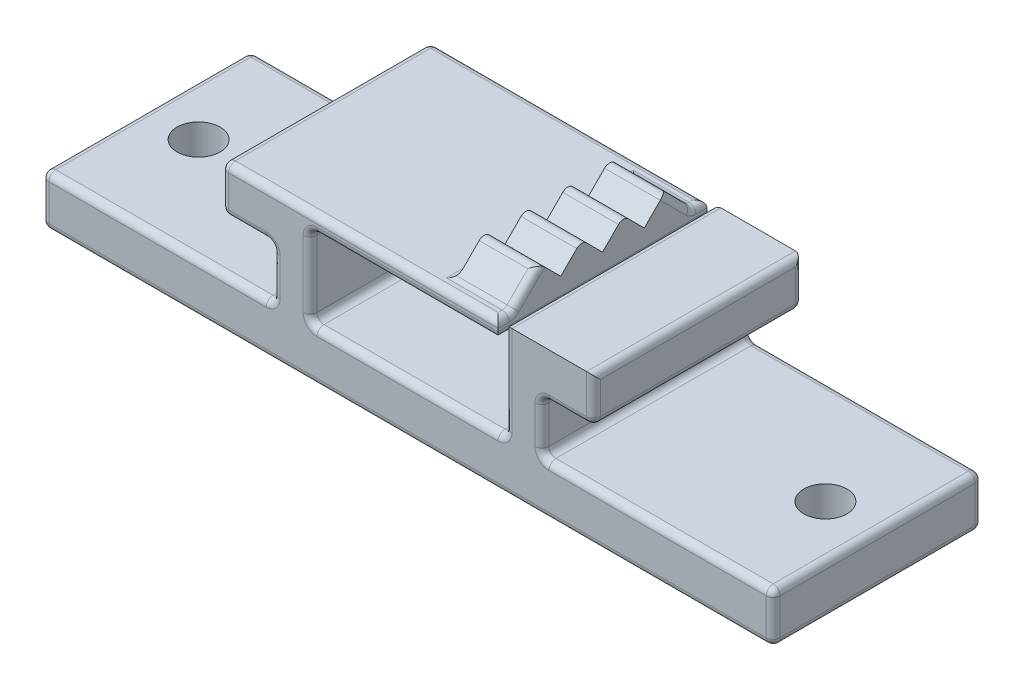
SolidWorks part; units mm, degrees
ref_plane "Front Plane" through (0, 0, 0) normal (0, 0, 1) x (1, 0, 0)
ref_plane "Top Plane" through (0, 0, 0) normal (0, 1, 0) x (1, 0, 0)
ref_plane "Right Plane" through (0, 0, 0) normal (1, 0, 0) x (0, 0, -1)
sketch "Sketch2" plane through (0, 0, 0) normal (0, 0, 1) x (1, 0, 0)
  line L0 (-88.9213, 72.576) -> (-88.9213, 68.976)
  line L1 (-36.4213, 72.576) -> (-36.4213, 68.976)
  line L3 (-88.9213, 72.576) -> (-36.4213, 72.576)
  line L5 (-88.9213, 68.976) -> (-36.4213, 68.976)
  line L8 (-53.0213, 72.576) -> (-53.0213, 76.276)
  line L9 (-53.0213, 76.276) -> (-49.3213, 76.276)
  line L10 (-49.3213, 76.276) -> (-49.3213, 79.576)
  line L11 (-49.3213, 79.576) -> (-76.0213, 79.576)
  line L12 (-62.6713, 57.576) -> (-62.6713, 72.576) construction
  line L13 (-72.3213, 72.576) -> (-72.3213, 76.276)
  line L14 (-72.3213, 76.276) -> (-76.0213, 76.276)
  line L15 (-76.0213, 76.276) -> (-76.0213, 79.576)
  point P6 (-62.6713, 79.576)
  point P21 (-62.6713, 72.576)
  point P24 (-62.6713, 68.976)
  dimension "D1" = 3.7
  dimension "D2" = 3.7
  dimension "D3" = 3.3
  dimension "D4" = 3.6
  dimension "D5" = 52.5
extrude "Boss-Extrude1" add sketch "Sketch2" along normal blind 15 contours L15 L14 L13 L3 L8 L9 L10 L11 | L12 L5 L1 L3 | L5 L12 L3 L0 region at (-75.7963, 70.776, 0) region at (-62.6713, 76.3592, 0) region at (-49.5463, 70.776, 0)
sketch "Sketch4" plane through (0, 0, 0) normal (0, 0, -1) x (-1, 0, 0)
  line L1 (69.6713, 72.576) -> (55.6713, 72.576)
  line L2 (69.6713, 72.576) -> (69.6713, 79.576)
  line L3 (69.6713, 79.576) -> (55.6713, 79.576)
  line L4 (55.6713, 72.576) -> (55.6713, 79.576)
  line L5 (62.6713, 57.576) -> (62.6713, 72.576) construction
  line L6 (49.3213, 79.576) -> (76.0213, 79.576) construction
  point P6 (62.6713, 72.576)
  dimension "D1" = 14
  dimension "D2" = 7
extrude "Cut-Extrude1" cut sketch "Sketch4" against normal through all
sketch "Sketch5" plane through (0, 79.576, 0) normal (0, 1, 0) x (1, 0, 0)
  line L1 (-69.6713, 0) -> (-56.1713, 0)
  line L2 (-69.6713, 0) -> (-69.6713, -15)
  line L3 (-69.6713, -15) -> (-56.1713, -15)
  line L4 (-56.1713, 0) -> (-56.1713, -15)
  line L6 (-69.6713, -15) -> (-76.0213, -15) construction
  point P9 (0, 0)
  dimension "D1" = 13.5
extrude "Boss-Extrude2" add sketch "Sketch5" against normal blind 1.2
sketch "Sketch6" plane through (-56.1713, 0, 0) normal (1, 0, 0) x (0, 0, -1)
  line L0 (-10.5, 80.076) -> (-12, 81.576)
  line L1 (-12, 81.576) -> (-13.5, 80.076)
  line L2 (-10.5, 80.076) -> (-13.5, 80.076)
  line L3 (-10.5, 80.076) -> (-10.5, 79.576)
  line L4 (-10.5, 79.576) -> (-13.5, 79.576)
  line L5 (-13.5, 79.576) -> (-13.5, 80.076)
  line L6 (-15, 79.576) -> (0, 79.576) construction
  point P7 (-13.5, 79.826)
  line M2 (0, 79.576) -> (-15, 79.576)
  dimension "D1" = 45
  dimension "D2" = 45
  dimension "D3" = 1.5
  dimension "D4" = 0.5
  dimension "D5" = 1.5
extrude "Boss-Extrude3" add sketch "Sketch6" against normal blind 4 contours L5 L3 L2 M2 | L2 L0 L1 region at (-56.1713, 80.576, 12) region at (-56.1713, 79.826, 12)
pattern_linear "LPattern1" count 4 spacing 3 along (0, 0, -1) of "Boss-Extrude3"
sketch "Sketch7" plane through (-56.1713, 0, 0) normal (1, 0, 0) x (0, 0, -1)
  line L0 (-13.5, 80.076) -> (-13.5, 79.576)
  line L1 (-13.5, 79.576) -> (-14, 79.576)
  line L2 (-15, 79.576) -> (-13.5, 79.576) construction
  line L3 (-14, 79.576) -> (-13.5, 80.076)
  line L4 (-1.5, 80.076) -> (-1.5, 79.576)
  line L5 (-1.5, 80.076) -> (-1.5, 79.576) construction
  line L6 (-1.5, 79.576) -> (0, 79.576) construction
  line L7 (-1.5, 79.576) -> (-1, 79.576)
  line L8 (-1, 79.576) -> (-1.5, 80.076)
  line L9 (-1.5, 80.076) -> (-1.5126, 80.0721)
  line L10 (-12, 81.576) -> (-13.5, 80.076) construction
  line L11 (-1.5, 80.076) -> (-3, 81.576) construction
extrude "Boss-Extrude4" add sketch "Sketch7" against normal blind 4 contours L4 L7 L8 | L3 L0 L1
fillet "Fillet1" radius 0.5 60 edges at (-56.1713, 80.576, 13) (-56.1713, 80.576, 2) (-62.9213, 78.376, 0) (-62.9213, 78.376, 15) (-62.6713, 72.576, 15) (-62.6713, 72.576, 0) (-44.7213, 72.576, 15) (-44.7213, 72.576, 0) (-51.1713, 76.276, 15) (-51.1713, 76.276, 0) (-74.1713, 76.276, 15) (-74.1713, 76.276, 0) (-80.6213, 72.576, 15) (-80.6213, 72.576, 0) (-56.1713, 79.576, 14.5) (-66.0963, 79.576, 15) (-66.0963, 79.576, 0) (-56.1713, 79.576, 0.5) (-58.1713, 79.576, 1) (-60.1713, 79.576, 7.5) (-58.1713, 79.576, 14) (-88.9213, 72.576, 7.5) (-88.9213, 70.776, 15) (-88.9213, 70.776, 0) (-36.4213, 70.776, 15) (-36.4213, 72.576, 7.5) (-36.4213, 70.776, 0) (-88.9213, 68.976, 7.5) (-62.6713, 68.976, 15) (-36.4213, 68.976, 7.5) (-62.6713, 68.976, 0) (-69.6713, 75.476, 0) (-69.6713, 72.576, 7.5) (-69.6713, 75.476, 15) (-69.6713, 78.376, 7.5) (-55.6713, 79.576, 7.5) (-55.6713, 76.076, 15) (-55.6713, 72.576, 7.5) (-55.6713, 76.076, 0) (-53.0213, 72.576, 7.5) (-53.0213, 74.426, 15) (-53.0213, 76.276, 7.5) (-53.0213, 74.426, 0) (-49.3213, 76.276, 7.5) (-49.3213, 77.926, 15) (-49.3213, 79.576, 7.5) (-49.3213, 77.926, 0) (-72.3213, 76.276, 7.5) (-72.3213, 74.426, 15) (-72.3213, 72.576, 7.5) (-72.3213, 74.426, 0) (-76.0213, 79.576, 7.5) (-76.0213, 77.926, 15) (-76.0213, 76.276, 7.5) (-76.0213, 77.926, 0) (-56.1713, 78.376, 7.5) (-58.1713, 81.576, 12) (-58.1713, 81.576, 9) (-58.1713, 81.576, 6) (-58.1713, 81.576, 3)
sketch "Sketch8" plane through (0, 68.976, 0) normal (0, -1, 0) x (1, 0, 0)
  line L0 (-36.9213, 0.5) -> (-36.9213, 14.5) construction
  line L1 (-40.1713, 7.5) -> (-85.1713, 7.5) construction
  circle A0 centre (-85.1713, 7.5) radius 1.55
  circle A1 centre (-40.1713, 7.5) radius 1.55
  point P4 (-62.6713, 7.5)
  point P7 (-36.9213, 7.5)
  point P8 (-45.8286, 7.5)
  dimension "D2" = 3.1
  dimension "D3" = 3.1
  dimension "D1" = 45
extrude "Cut-Extrude2" cut sketch "Sketch8" against normal through all
